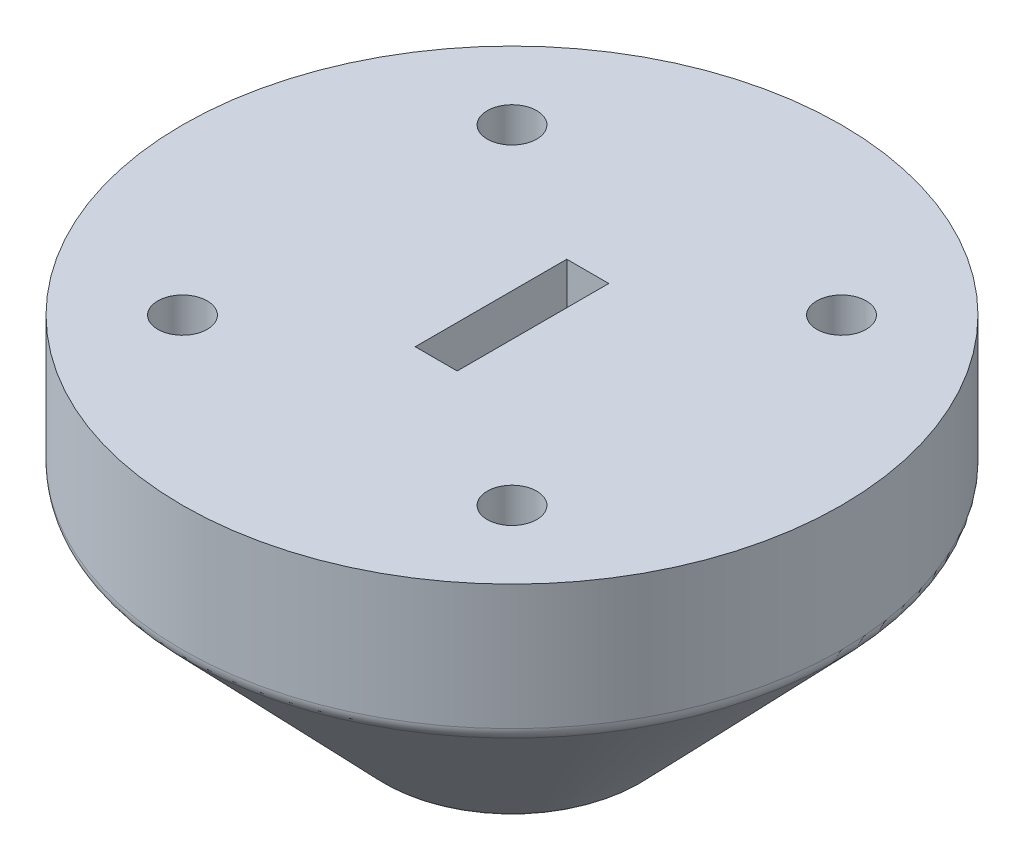
SolidWorks part; units mm, degrees
ref_plane "Front Plane" through (0, 0, 0) normal (0, 0, 1) x (1, 0, 0)
ref_plane "Top Plane" through (0, 0, 0) normal (0, 1, 0) x (1, 0, 0)
ref_plane "Right Plane" through (0, 0, 0) normal (1, 0, 0) x (0, 0, -1)
sketch "Sketch1" plane through (0, 0, 0) normal (0, 0, 1) x (1, 0, 0)
  line L0 (0, 0) -> (40, 0)
  line L1 (40, 0) -> (40, -16)
  line L2 (40, -16) -> (15, -42)
  line L3 (15, -42) -> (0, -42)
  line L4 (0, -42) -> (0, 0)
  dimension "D1" = 42
  dimension "D2" = 40
  dimension "D3" = 15
  dimension "D4" = 16
revolve "Revolve1" add sketch "Sketch1" angle 360 about L4
hole_wizard "Ø6.0mm Dowel Hole7" positions "Sketch9" profile "Sketch10" hole size "Ø5.0" standard "ISO"
sketch "Sketch9" plane through (0, 0, 0) normal (0, 1, 0) x (1, 0, 0)
  line L1 (-20, 20) -> (20, 20) construction
  line L2 (-20, 20) -> (-20, -20) construction
  line L3 (-20, -20) -> (20, -20) construction
  line L4 (20, 20) -> (20, -20) construction
  line L5 (-20, 20) -> (20, -20) construction
  line L6 (-20, -20) -> (20, 20) construction
  line L7 (0, 0) -> (0, -17.1882) construction
  line L8 (0, 0) -> (12.5207, 0) construction
  point P2 (20, -20)
  point P191 (-20, 20)
  point P192 (-20, -20)
  point P193 (20, 20)
  dimension "D1" = 40
  dimension "D2" = 40
sketch "Sketch10" plane through (20, 0, 20) normal (1, 0, 0) x (0, 0, 1)
  line L0 (0, 0) -> (0, 15)
  line L1 (0, 15) -> (3, 12)
  line L2 (3, 12) -> (3, 0)
  line L5 (3, 0) -> (0, 0)
  line L10 (0, 15) -> (-3, 12) construction
  line L11 (0, -6.35) -> (0, 107.95) construction
  dimension "Hole Dia." = 6
  dimension "Hole Depth" = 12
  dimension "Drill Angle" = 90
sketch "Sketch13" plane through (0, 0, 0) normal (0, 0, 1) x (1, 0, 0)
  line L0 (0, 0) -> (0, -42) construction
  line L1 (-15, -42) -> (15, -42) construction
  line L2 (-2.55, 0) -> (2.55, 0)
  line L3 (40, 0) -> (-40, 0) construction
  line L4 (2.55, 0) -> (2.55, -20)
  line L5 (-2.55, 0) -> (-2.55, -20)
  line L6 (2.55, -20) -> (1, -40)
  line L7 (-2.55, -20) -> (-1, -40)
  line L8 (1, -40) -> (-1, -40)
  point P13 (0, -40)
  dimension "D1" = 20
  dimension "D2" = 5.1
  dimension "D3" = 2
  dimension "D4" = 20
extrude "Cut-Extrude1" cut sketch "Sketch13" against normal blind 9.2 and the other way blind 9.2
fillet "Fillet1" radius 2 1 edges at (0, -42, -15)
fillet "Fillet2" radius 2 1 edges at (0, -16, -40)
fillet "Fillet6" radius 1 1 edges at (1, -40, 0)
fillet "Fillet7" radius 1 1 edges at (-1, -40, 0)
sketch "Sketch14" plane through (0, 0, 0) normal (1, 0, 0) x (0, 0, -1)
  line L0 (9.2, -39.0773) -> (9.2, -20) construction
  line L1 (9.2, -30) -> (12.2, -27)
  line L2 (12.2, -27) -> (9.2, -24)
  line L3 (9.2, -24) -> (6.2, -27)
  line L4 (6.2, -27) -> (9.2, -30)
  line L5 (40, 0) -> (-40, 0) construction
  circle A0 centre (9.2, -27) radius 2.1213 construction
  point P10 (0, 0)
  point P11 (0, 0)
  dimension "D1" = 24
  dimension "D2" = 6
extrude "Boss-Extrude1" add sketch "Sketch14" along normal blind 10 and the other way blind 10
fillet "Fillet8" radius 1 1 edges at (0, -27, -6.2)
